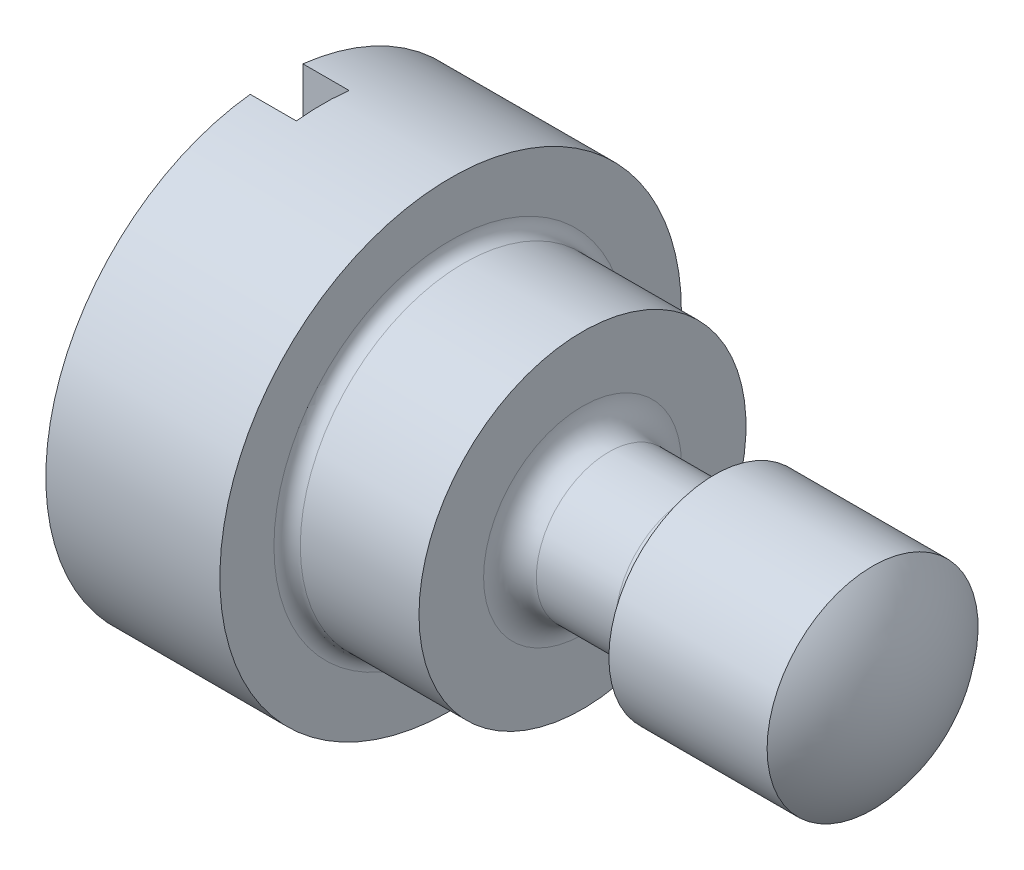
SolidWorks part; units mm, degrees
ref_plane "Front" through (0, 0, 0) normal (0, 0, 1) x (1, 0, 0)
ref_plane "Top" through (0, 0, 0) normal (0, 1, 0) x (1, 0, 0)
ref_plane "Right" through (0, 0, 0) normal (1, 0, 0) x (0, 0, -1)
sketch "Sketch1" plane through (0, 0, 0) normal (1, 0, 0) x (0, 0, -1)
  circle A0 centre (0, 0) radius 1.75
extrude "BaseHead" add sketch "Sketch1" along normal blind 1.32
sketch "Sketch2" plane through (0.1968, 0, 0.1968) normal (0, 1, 0) x (0, 0, 1)
  line L1 (-0.3968, -0.1968) -> (0.0032, -0.1968)
  line L2 (-0.3968, -0.1968) -> (-0.3968, 0.1532)
  line L3 (-0.3968, 0.1532) -> (0.0032, 0.1532)
  line L4 (0.0032, -0.1968) -> (0.0032, 0.1532)
  line L5 (-0.1968, -1.4104) -> (-0.1968, 1.0169) construction
  dimension "t" = 0.35
  dimension "n" = 0.4
extrude "Slot" cut sketch "Sketch2" against normal through all and the other way through all
sketch "Sketch4" plane through (0, 0, 0) normal (0, 0, 1) x (1, 0, 0)
  line L0 (-0.6595, 0) -> (4.82, 0) construction
  line L1 (1.32, 1.24) -> (2.32, 1.24)
  line L2 (4.82, 0) -> (1.32, 0)
  line L3 (1.32, -1.75) -> (1.32, 1.75) construction
  line L4 (1.32, 1.24) -> (1.32, 0)
  line L5 (3.32, 0.8) -> (4.52, 0.8)
  line L6 (2.32, 1.24) -> (2.32, 0.75)
  line L9 (2.52, 0.55) -> (3.12, 0.55)
  line L10 (3.32, 0.75) -> (3.32, 0.8)
  arc A0 (4.52, 0.8) -> (4.82, 0) centre (3.6033, 0) cw
  arc A1 (2.32, 0.75) -> (2.52, 0.55) centre (2.52, 0.75) ccw
  arc A2 (3.12, 0.55) -> (3.32, 0.75) centre (3.12, 0.75) ccw
  dimension "r1" = 0.2
  dimension "s" = 0.3
  dimension "l" = 1
revolve "BaseBody" add sketch "Sketch4" angle 360 about L0
cosmetic thread "ThreadCosmetic1" [suppressed] parameters "D2"=1.221
fillet "Fillet1" radius 0.1 1 edges at (1.32, 0, 1.24)
sketch "Sketch5" plane through (0, 0, 0) normal (0, 0, 1) x (1, 0, 0)
  line L0 (4.52, 0.6359) -> (4.6147, 0.8)
  line L1 (4.6147, 0.8) -> (4.6147, 0.9895)
  line L2 (4.6147, 0.9895) -> (4.4252, 0.9895)
  line L3 (4.4252, 0.9895) -> (4.4252, 0.8)
  line L4 (4.4252, 0.8) -> (4.52, 0.6359)
  line L5 (0, 0) -> (6.0976, 0) construction
  line L6 (4.52, 0.8) -> (4.52, -0.8) construction
  line L7 (4.52, 0.8) -> (3.32, 0.8) construction
  dimension "D1" = 0.1895
revolve "Cut-Revolve10" [suppressed] cut sketch "Sketch5" angle 360 about L5
pattern_linear "LPattern10" [suppressed] count 7 spacing 0.2274 along (-1, 0, 0) of bodies 106
equation "\"D1@Sketch5\" = (  \"d@Sketch4\" - \"D2@ThreadCosmetic1\" )  / 2"
equation "\"D3@LPattern10\" = \"D1@Sketch5\" * 1.2"
equation "\"D1@LPattern10\" =  ( \"b@Sketch4\" - \"a@Sketch4\" )  / \"D3@LPattern10\""
